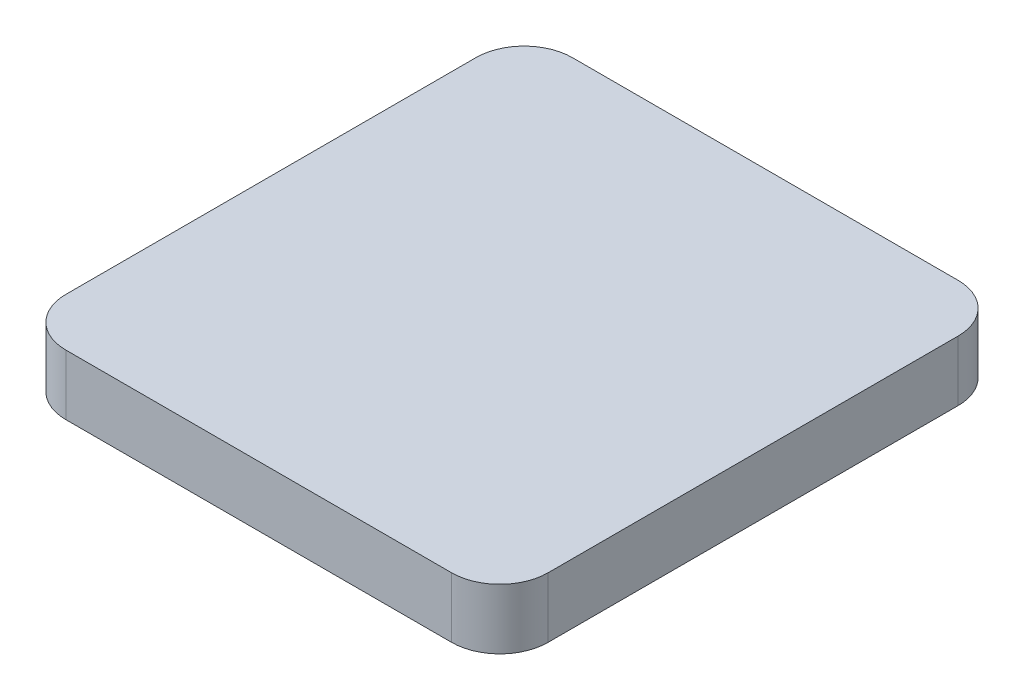
SolidWorks part; units mm, degrees
material "Acrylic (Medium-high impact)"
ref_plane "Front Plane" through (0, 0, 0) normal (0, 0, 1) x (1, 0, 0)
ref_plane "Top Plane" through (0, 0, 0) normal (0, 1, 0) x (1, 0, 0)
ref_plane "Right Plane" through (0, 0, 0) normal (1, 0, 0) x (0, 0, -1)
ref_plane "Plane1" through (0, 0, 0) normal (0, 1, 0) x (1, 0, 0)
sketch "Sketch1" plane through (0, 0, 0) normal (0, 1, 0) x (1, 0, 0)
  line L1 (0, 0) -> (25.4, 0)
  line L2 (0, 0) -> (0, 26.68)
  line L3 (0, 26.68) -> (25.4, 26.68)
  line L4 (25.4, 0) -> (25.4, 26.68)
  dimension "D1" = 26.68
  dimension "D2" = 25.4
extrude "Boss-Extrude1" add sketch "Sketch1" along normal blind 3.175
ref_plane "Plane2" through (0, 3.175, 0) normal (0, 1, 0) x (1, 0, 0)
sketch "Sketch2" plane through (0, 3.175, 0) normal (0, 1, 0) x (1, 0, 0)
  line L0 (0, 26.68) -> (0, 0) construction
  line L1 (6.35, 17.155) -> (19.05, 17.155)
  line L2 (6.35, 17.155) -> (6.35, 20.33)
  line L3 (6.35, 20.33) -> (19.05, 20.33)
  line L4 (19.05, 17.155) -> (19.05, 20.33)
  line L5 (25.4, 0) -> (25.4, 26.68) construction
  line L7 (25.4, 26.68) -> (0, 26.68) construction
  dimension "D1" = 6.35
  dimension "D2" = 6.35
  dimension "D3" = 6.35
  dimension "D4" = 3.175
extrude "Cut-Extrude1" [suppressed] cut sketch "Sketch2" against normal through all
fillet "Fillet1" radius 2.54 4 edges at (0, 1.5875, -26.68) (25.4, 1.5875, -26.68) (25.4, 1.5875, 0) (0, 1.5875, 0)
